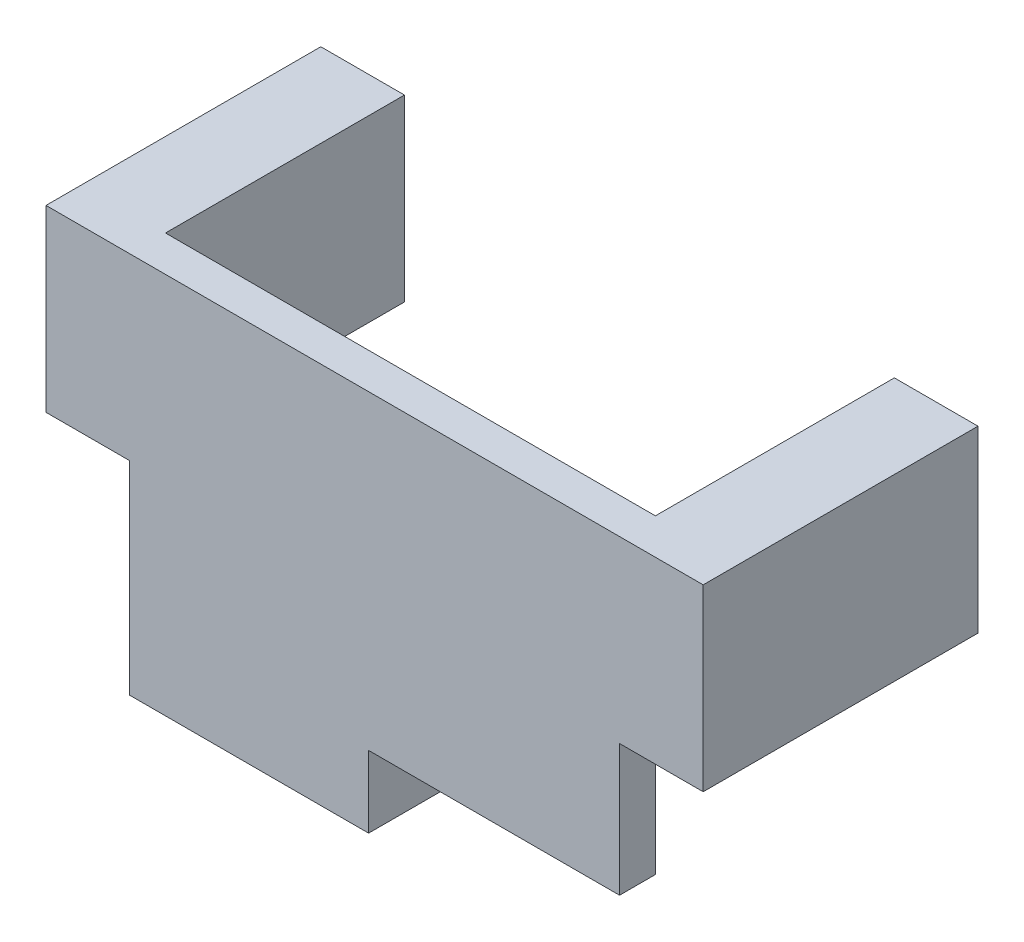
SolidWorks part; units mm, degrees
ref_plane "Front Plane" through (0, 0, 0) normal (0, 0, 1) x (1, 0, 0)
ref_plane "Top Plane" through (0, 0, 0) normal (0, 1, 0) x (1, 0, 0)
ref_plane "Right Plane" through (0, 0, 0) normal (1, 0, 0) x (0, 0, -1)
sketch "Sketch1" plane through (0, 0, 0) normal (0, 0, 1) x (1, 0, 0)
  line L0 (0, 0) -> (0, 32.6763) construction
  line L1 (-20.5, -13) -> (20.5, -13)
  line L2 (-20.5, -13) -> (-20.5, 13)
  line L3 (-20.5, 13) -> (20.5, 13)
  line L4 (20.5, -13) -> (20.5, 13)
  line L5 (-20.5, -13) -> (20.5, 13) construction
  line L6 (-20.5, 13) -> (20.5, -13) construction
  line L11 (-20.5, -2) -> (-27.5, -2)
  line L12 (20.5, 13) -> (27.5, 13)
  line L13 (20.5, 13) -> (20.5, -2)
  line L14 (20.5, 13) -> (20.5, -13)
  line L15 (20.5, -2) -> (27.5, -2)
  line L24 (27.5, 13) -> (27.5, -2)
  line L25 (-27.5, 13) -> (-27.5, -2)
  line L26 (-20.5, 13) -> (-27.5, 13)
  line L27 (-20.5, 13) -> (-20.5, -2)
  line L29 (-20.5, -13) -> (-0.5, -13)
  line L30 (-20.5, -13) -> (-20.5, -19)
  line L31 (-20.5, -19) -> (-0.5, -19)
  line L32 (-0.5, -13) -> (-0.5, -19)
  point P0 (0, 0)
  dimension "D1" = 41
  dimension "D2" = 26
  dimension "D3" = 11
  dimension "D4" = 7
  dimension "D5" = 6
  dimension "D6" = 20
extrude "Boss-Extrude1" add sketch "Sketch1" against normal blind 3 contours L1 L4 L3 L2 region at (0, 0, 0)
extrude "Boss-Extrude2" add sketch "Sketch1<3>" against normal offset from surface (23 mm away) 20 contours L4 | L1 L25 | L15 L2 region at (-10.5, -16, 0) region at (-24, 5.5, 0) region at (24, 5.5, 0) up to face at (0, 0, -3) offset beyond the face yes
sketch "Sketch1<3>" plane through (0, 0, 0) normal (0, 0, 1) x (1, 0, 0) same geometry as "Sketch1"
